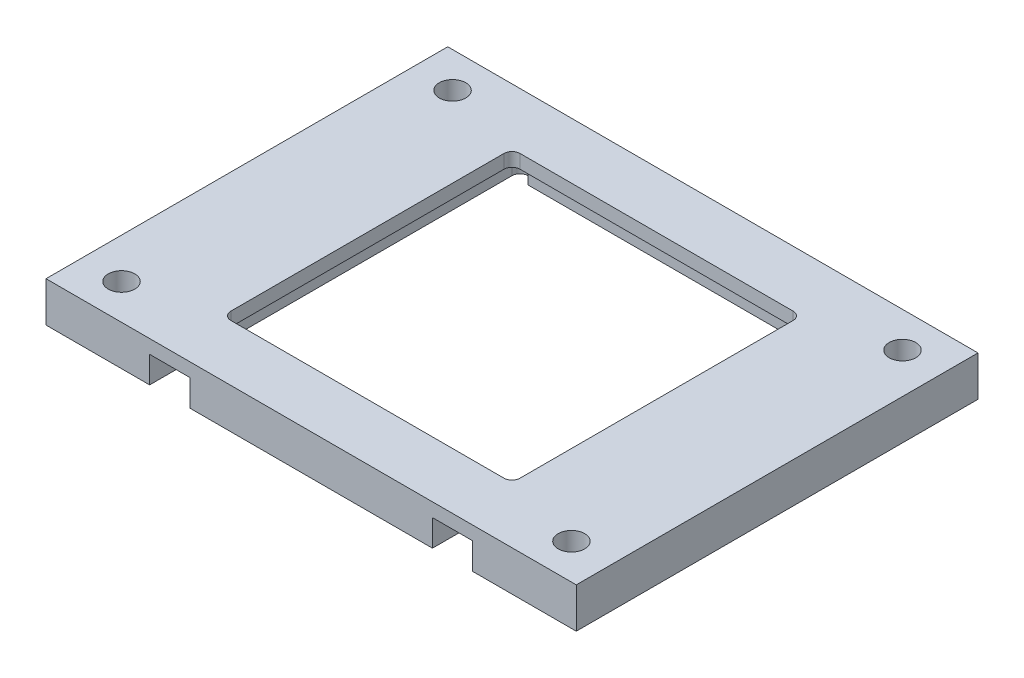
SolidWorks part; units mm, degrees
ref_plane "Front Plane" through (0, 0, 0) normal (0, 0, 1) x (1, 0, 0)
ref_plane "Top Plane" through (0, 0, 0) normal (0, 1, 0) x (1, 0, 0)
ref_plane "Right Plane" through (0, 0, 0) normal (1, 0, 0) x (0, 0, -1)
sketch "Sketch1" plane through (0, 0, 0) normal (0, 1, 0) x (1, 0, 0)
  line L0 (20.1, -20.1) -> (20.1, 21.1)
  line L1 (-20.1, -20.1) -> (20.1, -20.1)
  line L3 (-18.1, 20.1) -> (18.1, 20.1)
  line L5 (-20.1, 21.1) -> (-20.1, -20.1)
  line L7 (-33, -25) -> (33, -25)
  line L8 (-33, -25) -> (-33, 25)
  line L9 (-33, 25) -> (33, 25)
  line L10 (33, -25) -> (33, 25)
  line L11 (-33, -25) -> (33, 25) construction
  line L12 (-33, 25) -> (33, -25) construction
  line L15 (-20.1, 21.1) -> (-18.1, 21.1)
  line L16 (-18.1, 20.1) -> (-18.1, 21.1)
  line L19 (20.1, 21.1) -> (18.1, 21.1)
  line L20 (18.1, 20.1) -> (18.1, 21.1)
  circle A0 centre (-28, 20.6) radius 1.65
  circle A1 centre (28, 20.6) radius 1.65
  circle A2 centre (-28, -20.6) radius 1.65
  circle A3 centre (28, -20.6) radius 1.65
  point P0 (0, 0)
  point P15 (0, 0)
  dimension "D3" = 20.6
  dimension "D4" = 20.6
  dimension "D5" = 20.6
  dimension "D6" = 20.6
  dimension "D7" = 28
  dimension "D10" = 28
  dimension "D11" = 3.3
  dimension "D14" = 2
  dimension "D2" = 40.2
  dimension "D8" = 28
  dimension "D9" = 28
  dimension "D12" = 66
  dimension "D13" = 50
  dimension "D15" = 1
  dimension "D16" = 2
  dimension "D17" = 1
  dimension "D18" = 20.1
  dimension "D19" = 40.2
  dimension "D20" = 20.1
extrude "Boss-Extrude1" add sketch "Sketch1" along normal blind 5
sketch "Sketch2" plane through (0, 5, 0) normal (0, 1, 0) x (1, 0, 0)
  line L12 (-18, -18) -> (18, -18)
  line L13 (18, -18) -> (18, 18)
  line L14 (-18, 18) -> (-18, -18)
  line L15 (18, 18) -> (-18, 18)
  line L54 (-20.1, 21.1) -> (-20.1, -20.1)
  line L55 (-20.1, -20.1) -> (20.1, -20.1)
  line L56 (20.1, -20.1) -> (20.1, 21.1)
  line L57 (20.1, 21.1) -> (18.1, 21.1)
  line L58 (18.1, 21.1) -> (18.1, 20.1)
  line L59 (18.1, 20.1) -> (-18.1, 20.1)
  line L60 (-18.1, 20.1) -> (-18.1, 21.1)
  line L61 (-18.1, 21.1) -> (-20.1, 21.1)
  line L62 (-20.1, 21.1) -> (-20.1, -20.1)
  line L63 (-20.1, -20.1) -> (20.1, -20.1)
  line L64 (20.1, -20.1) -> (20.1, 21.1)
  line L65 (20.1, 21.1) -> (18.1, 21.1)
  line L66 (18.1, 21.1) -> (18.1, 20.1)
  line L67 (18.1, 20.1) -> (-18.1, 20.1)
  line L68 (-18.1, 20.1) -> (-18.1, 21.1)
  line L69 (-18.1, 21.1) -> (-20.1, 21.1)
  dimension "D1" = 36
  dimension "D3" = 36
  dimension "D4" = 18
  dimension "D5" = 18
  dimension "D6" = 36
  dimension "D7" = 36
  dimension "D2" = 0
extrude "Boss-Extrude2" add sketch "Sketch2" against normal blind 1.7
sketch "Sketch3" plane through (0, 0, 25) normal (0, 0, 1) x (1, 0, 0)
  line L0 (-33, 0) -> (33, 0) construction
  line L1 (-20.1, 0) -> (-15.1, 0)
  line L3 (-20.1, 3.3) -> (-15.1, 3.3)
  line L4 (-15.1, 0) -> (-15.1, 3.3)
  line L5 (20.1, 0) -> (20.1, 3.3)
  line L6 (20.1, 0) -> (15.1, 0)
  line L8 (20.1, 3.3) -> (15.1, 3.3)
  line L9 (15.1, 0) -> (15.1, 3.3)
  line L10 (-20.1, 0) -> (-20.1, 3.3)
  dimension "D1" = 5
  dimension "D2" = 5
  dimension "D3" = 0
  dimension "D4" = 0
  dimension "D5" = 3.3
  dimension "D6" = 3.3
extrude "Cut-Extrude1" cut sketch "Sketch3" against normal up to next
fillet "Fillet1" radius 1 8 edges at (-18, 4.15, 18) (18, 4.15, 18) (18, 4.15, -18) (-18, 4.15, -18) (-20.1, 1.65, -21.1) (-18.1, 1.65, -21.1) (18.1, 1.65, -21.1) (20.1, 1.65, -21.1)
